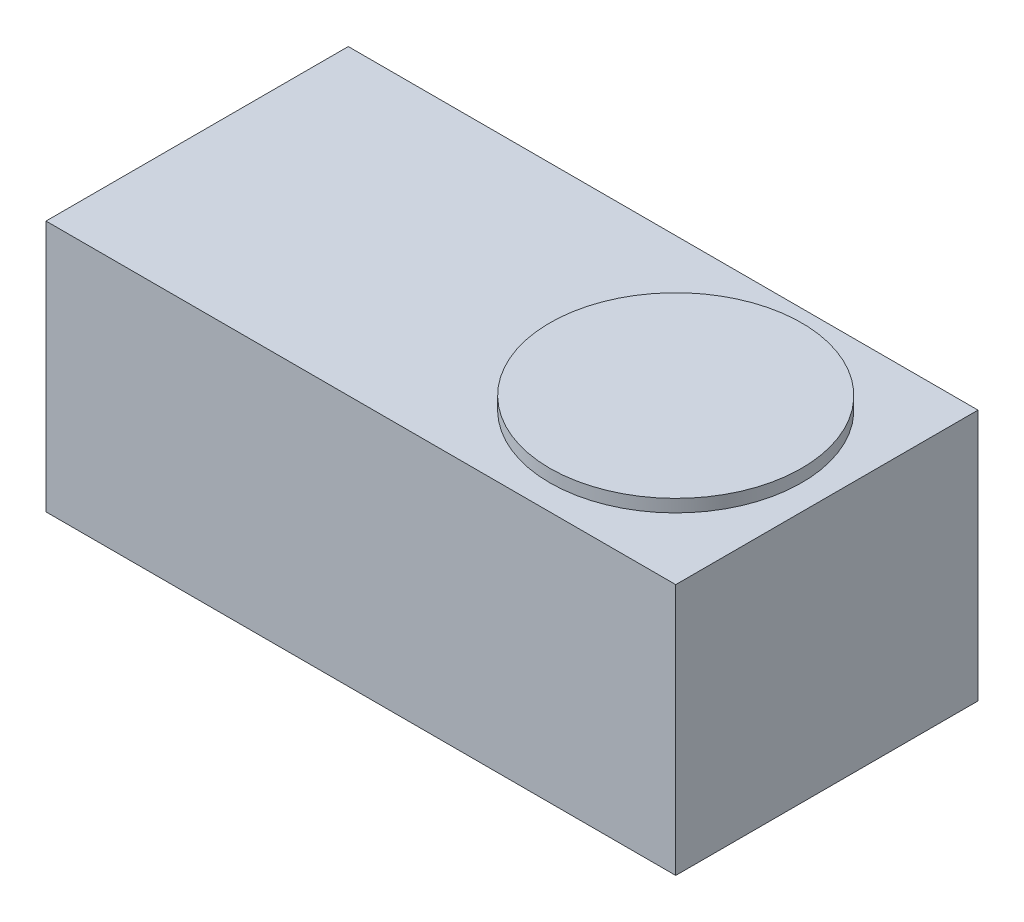
SolidWorks part; units mm, degrees
ref_plane "Front Plane" through (0, 0, 0) normal (0, 0, 1) x (1, 0, 0)
ref_plane "Top Plane" through (0, 0, 0) normal (0, 1, 0) x (1, 0, 0)
ref_plane "Right Plane" through (0, 0, 0) normal (1, 0, 0) x (0, 0, -1)
ref_axis "Axis1" through (0, 1.05, 0) along (0, -1, 0)
ref_plane "Plane1" through (0, -1, 0) normal (0, 1, 0) x (1, 0, 0)
sketch "Sketch2" plane through (0, 0, 0) normal (0, 1, 0) x (1, 0, 0)
  circle A0 centre (0, 0) radius 10
  dimension "D1" = 20
extrude "Boss-Extrude1" add sketch "Sketch2" against normal up to surface (1 mm away) up to plane "Plane1"
sketch "Sketch4" plane through (0, -1, 0) normal (0, 1, 0) x (1, 0, 0)
  line L0 (-38, 0) -> (12, 0) construction
  line L1 (12, 12) -> (-38, 12)
  line L2 (12, 12) -> (12, -12)
  line L3 (12, -12) -> (-38, -12)
  line L4 (-38, 12) -> (-38, -12)
  dimension "D1" = 12
  dimension "D2" = 12
  dimension "D3" = 50
extrude "Boss-Extrude2" add sketch "Sketch4" against normal blind 20
